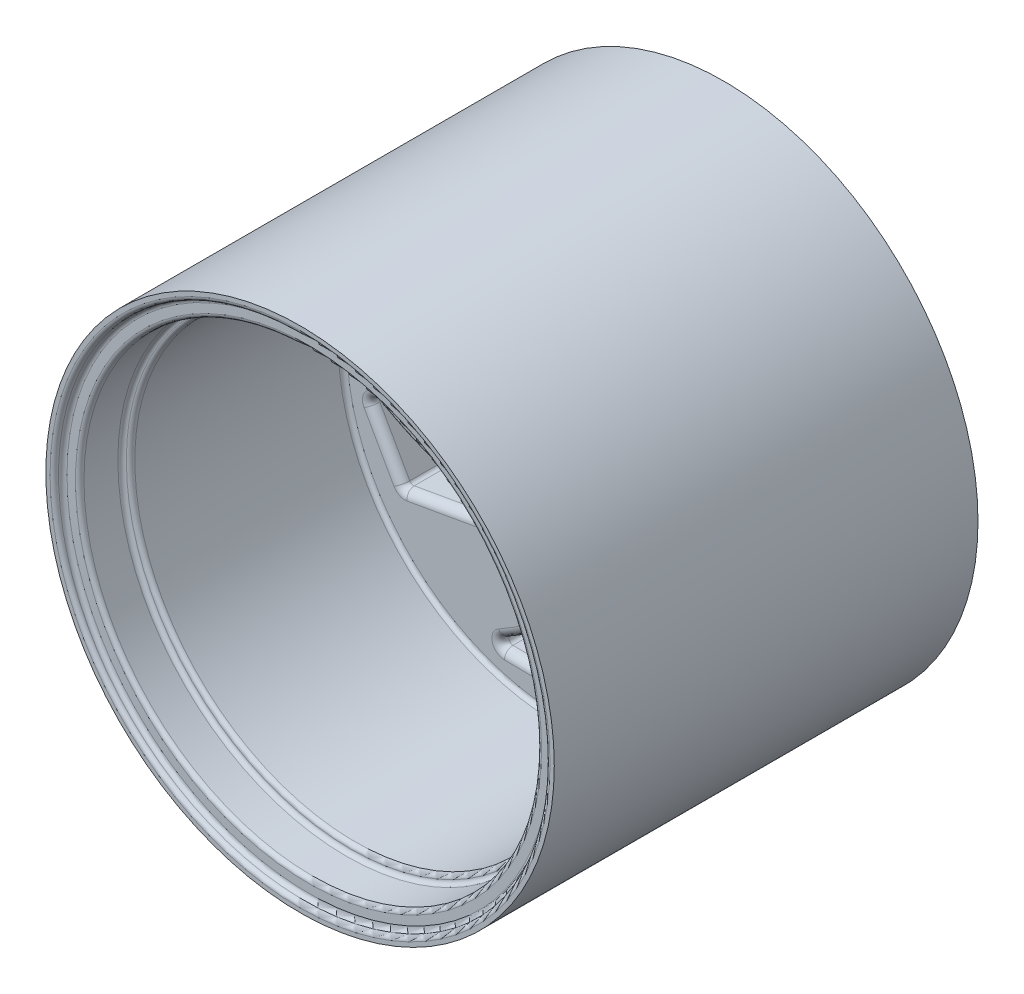
SolidWorks part; units mm, degrees
ref_plane "Ön Düzlem" through (0, 0, 0) normal (0, 0, 1) x (1, 0, 0)
ref_plane "Üst Düzlem" through (0, 0, 0) normal (0, 1, 0) x (1, 0, 0)
ref_plane "Sağ Düzlem" through (0, 0, 0) normal (1, 0, 0) x (0, 0, -1)
sketch "Çizim1" plane through (0, 0, 0) normal (0, 0, 1) x (1, 0, 0)
  circle A0 centre (-8.1488, -1.5541) radius 30
  dimension "D1" = 60
extrude "Yükseklik-Ekstrüzyon1" add sketch "Çizim1" along normal blind 50
sketch "Çizim2" plane through (0, 0, 0) normal (0, 0, -1) x (-1, 0, 0)
  circle A0 centre (8.1488, -1.5541) radius 29
  circle A1 centre (8.1488, -1.5541) radius 30 construction
  dimension "D1" = 1
extrude "Kes-Ekstrüzyon1" cut sketch "Çizim2" against normal blind 1
sketch "Çizim3" plane through (0, 0, 50) normal (0, 0, 1) x (1, 0, 0)
  circle A0 centre (-8.1488, -1.5541) radius 29
  circle A1 centre (-8.1488, -1.5541) radius 30 construction
  dimension "D1" = 1
extrude "Kes-Ekstrüzyon2" cut sketch "Çizim3" against normal blind 1
sketch "Çizim4" plane through (0, 0, 49) normal (0, 0, 1) x (1, 0, 0)
  circle A0 centre (-8.1488, -1.5541) radius 27
  circle A1 centre (-8.1488, -1.5541) radius 29 construction
  dimension "D1" = 2
extrude "Kes-Ekstrüzyon3" cut sketch "Çizim4" against normal blind 5
sketch "Çizim5" plane through (0, 0, 44) normal (0, 0, 1) x (1, 0, 0)
  circle A0 centre (-8.1488, -1.5541) radius 26
  circle A1 centre (-8.1488, -1.5541) radius 27 construction
  dimension "D1" = 1
extrude "Kes-Ekstrüzyon4" cut sketch "Çizim5" against normal blind 25
sketch "Çizim6" plane through (0, 0, 19) normal (0, 0, 1) x (1, 0, 0)
  circle A0 centre (-8.1488, -1.5541) radius 10
  circle A1 centre (-8.1488, -1.5541) radius 8
  circle A2 centre (-8.1488, 4.4459) radius 1
  circle A3 centre (-3.9061, 2.6885) radius 1
  circle A4 centre (-2.1488, -1.5541) radius 1
  circle A5 centre (-3.9061, -5.7967) radius 1
  circle A6 centre (-8.1488, -7.5541) radius 1
  circle A7 centre (-12.3914, -5.7967) radius 1
  circle A8 centre (-14.1488, -1.5541) radius 1
  circle A9 centre (-12.3914, 2.6885) radius 1
  point P23 (-8.1488, -1.5541)
  dimension "D1" = 20
  dimension "D2" = 2
  dimension "D3" = 2
  dimension "D4" = 6
  dimension "D5" = 8
ref_axis "Eksen1" through (-8.1488, -1.5541, 50) along (0, 0, -1)
extrude "Yükseklik-Ekstrüzyon2" add sketch "Çizim6" along normal blind 2 contours A0 A1 | A2 | A8 | A7 | A6 | A5 | A3 | A9 | A4 region at (-17.8659, -1.5541, 19) region at (-8.1488, 4.4459, 19) region at (-3.9061, 2.6885, 19) region at (-3.9061, -5.7967, 19) region at (-8.1488, -7.5541, 19) region at (-12.3914, -5.7967, 19) region at (-14.1488, -1.5541, 19)
sketch "Çizim8" plane through (0, 0, 19) normal (0, 0, 1) x (1, 0, 0)
  circle A0 centre (-8.1488, -1.5541) radius 2
  dimension "D1" = 4
extrude "Kes-Ekstrüzyon5" cut sketch "Çizim8" against normal through all
sketch "Çizim9" plane through (0, 0, 19) normal (0, 0, 1) x (1, 0, 0)
  line L0 (-13.9257, 6.6084) -> (-8.8336, 20.6384)
  line L1 (-8.8336, 20.6384) -> (0.7231, 20.5255)
  line L3 (-3.9683, 7.5301) -> (10.7281, 10.1352)
  line L4 (10.7281, 10.1352) -> (15.4086, 1.8024)
  line L5 (1.8086, -0.6324) -> (11.4129, -12.0573)
  line L6 (11.4129, -12.0573) -> (6.5368, -20.2771)
  line L7 (-2.3718, -9.7166) -> (-7.464, -23.7466)
  line L8 (-7.464, -23.7466) -> (-17.0206, -23.6337)
  line L9 (-12.3293, -10.6383) -> (-27.0257, -13.2434)
  line L10 (-27.0257, -13.2434) -> (-31.7062, -4.9106)
  line L11 (-18.1062, -2.4758) -> (-27.7105, 8.9491)
  line L12 (-30.8072, 6.6742) -> (-25.9311, 14.894) [skipped]
  line L13 (-21.203, -4.7508) -> (-30.8072, 6.6742) [skipped]
  line L14 (-29.7006, -19.3377) -> (-34.3811, -11.0049) [skipped]
  line L15 (-15.0042, -16.7326) -> (-29.7006, -19.3377) [skipped]
  line L16 (-1.5282, -17.3553) -> (-6.6204, -31.3853) [skipped]
  line L17 (-6.6204, -31.3853) -> (-16.177, -31.2724) [skipped]
  line L18 (5.749, -5.9961) -> (15.3533, -17.421) [skipped]
  line L19 (15.3533, -17.421) -> (10.4771, -25.6408) [skipped]
  line L20 (-0.4498, 5.9858) -> (14.2467, 8.5908) [skipped]
  line L21 (14.2467, 8.5908) -> (18.9272, 0.2581) [skipped]
  line L22 (-27.7105, 8.9491) -> (-22.8343, 17.1689)
  circle A0 centre (-8.1488, -1.5541) radius 10 construction
  spline S0 degree 2 poles (0.7231, 20.5255) (-8.7276, 15.9675) (-13.9257, 6.6084) knots 0 0 0 1 1 1
  spline S1 degree 2 poles (15.4086, 1.8024) (6.7359, 7.708) (-3.9683, 7.5301) knots 0 0 0 1 1 1
  spline S2 degree 2 poles (6.5368, -20.2771) (7.3147, -9.8136) (1.8086, -0.6324) knots 0 0 0 1 1 1
  spline S3 degree 2 poles (-17.0206, -23.6337) (-7.5699, -19.0756) (-2.3718, -9.7166) knots 0 0 0 1 1 1
  spline S4 degree 2 poles (-31.7062, -4.9106) (-23.0335, -10.8162) (-12.3293, -10.6383) knots 0 0 0 1 1 1
  spline S5 degree 2 poles (-22.8343, 17.1689) (-23.6123, 6.7054) (-18.1062, -2.4758) knots 0 0 0 1 1 1
  point P29 (-7.727, -5.3734)
  point P55 (-8.1488, -1.5541)
  dimension "D1" = 6
  dimension "D2" = 6
extrude "Kes-Ekstrüzyon6" cut sketch "Çizim9" against normal through all
sketch "Çizim12" plane through (0, 0, 1) normal (0, 0, -1) x (-1, 0, 0)
  circle A0 centre (8.1488, -1.5541) radius 29
extrude "Kes-Ekstrüzyon7" cut sketch "Çizim12" against normal blind 10
sketch "Çizim13" plane through (0, 0, 11) normal (0, 0, -1) x (-1, 0, 0)
  line L0 (25.695, 21.5369) -> (26.0905, 21.2309)
  line L1 (13.3589, -5.1856) -> (13.8988, 1.1423)
  line L2 (13.8988, 1.1423) -> (8.6887, 4.7738)
  line L3 (8.6887, 4.7738) -> (2.9386, 2.0774)
  line L4 (2.9386, 2.0774) -> (2.3988, -4.2505)
  line L5 (2.3988, -4.2505) -> (7.6089, -7.882)
  line L6 (7.6089, -7.882) -> (13.3589, -5.1856)
  line L7 (13.239, 4.6176) -> (26.0905, 21.2309)
  line L8 (12.8435, 4.9235) -> (25.695, 21.5369)
  line L9 (16.1059, -2.3811) -> (36.9193, -5.2041)
  line L10 (16.0387, -2.8765) -> (36.8521, -5.6996)
  line L11 (36.9193, -5.2041) -> (36.8521, -5.6996)
  line L12 (11.4112, -8.8587) -> (19.373, -28.2951)
  line L13 (10.9485, -9.0482) -> (18.9103, -28.4846)
  line L14 (19.373, -28.2951) -> (18.9103, -28.4846)
  line L15 (3.454, -8.0317) -> (-9.3975, -24.6451)
  line L16 (3.0585, -7.7258) -> (-9.7929, -24.3391)
  line L17 (-9.3975, -24.6451) -> (-9.7929, -24.3391)
  line L18 (0.1916, -0.7271) -> (-20.6217, 2.0959)
  line L19 (0.2588, -0.2317) -> (-20.5545, 2.5914)
  line L20 (-20.6217, 2.0959) -> (-20.5545, 2.5914)
  line L21 (4.8864, 5.7505) -> (-3.0755, 25.1869)
  line L22 (5.3491, 5.94) -> (-2.6128, 25.3764)
  line L23 (-3.0755, 25.1869) -> (-2.6128, 25.3764)
  circle A0 centre (8.1488, -1.5541) radius 5.5 construction
  arc A1 (4.8864, 5.7505) -> (0.2588, -0.2317) centre (8.1488, -1.5541) ccw
  arc A2 (12.8435, 4.9235) -> (5.3491, 5.94) centre (8.1488, -1.5541) ccw
  arc A3 (0.1916, -0.7271) -> (3.0585, -7.7258) centre (8.1488, -1.5541) ccw
  arc A4 (3.454, -8.0317) -> (10.9485, -9.0482) centre (8.1488, -1.5541) ccw
  arc A5 (11.4112, -8.8587) -> (16.0387, -2.8765) centre (8.1488, -1.5541) ccw
  arc A6 (16.1059, -2.3811) -> (13.239, 4.6176) centre (8.1488, -1.5541) ccw
  point P37 (8.1488, -1.5541)
  dimension "D2" = 16
  dimension "D1" = 11
  dimension "D3" = 0.5
  dimension "D4" = 6
extrude "Yükseklik-Ekstrüzyon4" add sketch "Çizim13" along normal blind 10
fillet "Radyus1" radius 0.5 6 edges at (17.8512, -1.5541, 19) (20.8512, -1.5541, 50) (20.8512, -1.5541, 49) (18.8512, -1.5541, 49) (18.8512, -1.5541, 44) (17.8512, -1.5541, 44)
fillet "Radyus5" radius 0.5 18 edges at (-22.8343, 17.1689, 15) (-18.1062, -2.4758, 15) (-27.7105, 8.9491, 15) (-12.3293, -10.6383, 15) (-27.0257, -13.2434, 15) (-31.7062, -4.9106, 15) (-17.0206, -23.6337, 15) (-2.3718, -9.7166, 15) (-7.464, -23.7466, 15) (6.5368, -20.2771, 15) (1.8086, -0.6324, 15) (11.4129, -12.0573, 15) (-3.9683, 7.5301, 15) (15.4086, 1.8024, 15) (10.7281, 10.1352, 15) (0.7231, 20.5255, 15) (-13.9257, 6.6084, 15) (-8.8336, 20.6384, 15)
fillet "Radyus6" radius 1 36 edges at (14.3408, 2.944, 19) (12.6652, 6.6867, 19) (10.6798, 10.0329, 19) (5.4279, 9.1957, 19) (0.0646, 7.8091, 19) (-0.7995, 20.1716, 19) (-4.8785, 20.5917, 19) (-8.7692, 20.5454, 19) (-10.67, 15.5786, 19) (-12.1509, 10.2405, 19) (-23.2891, 15.6734, 19) (-25.6925, 12.3509, 19) (-27.5977, 8.9584, 19) (-24.2467, 4.8288, 19) (-20.3643, 0.8773, 19) (-30.6384, -6.0522, 19) (-28.9627, -9.7949, 19) (-26.9773, -13.1411, 19) (-21.7255, -12.3039, 19) (-16.3622, -10.9173, 19) (4.0667, -3.9855, 19) (7.9491, -7.937, 19) (11.3001, -12.0666, 19) (9.3949, -15.4591, 19) (6.9915, -18.7816, 19) (-4.1467, -13.3487, 19) (-5.6275, -18.6867, 19) (-7.5284, -23.6536, 19) (-11.419, -23.6999, 19) (-15.4981, -23.2798, 19)
fillet "Radyus7" radius 0.5 25 edges at (-17.233, 2.6264, 19) (-16.3113, -7.331, 19) (-7.2271, -11.5115, 19) (0.9355, -5.7346, 19) (0.0137, 4.2228, 19) (-9.0705, 8.4033, 19) (-2.9061, -5.7967, 21) (-11.3914, 2.6885, 21) (-11.3914, -5.7967, 19) (-13.1488, -1.5541, 19) (-11.3914, -5.7967, 21) (-7.1488, -7.5541, 19) (-7.1488, -7.5541, 21) (-2.9061, -5.7967, 19) (-1.1488, -1.5541, 19) (-1.1488, -1.5541, 21) (-2.9061, 2.6885, 21) (-7.1488, 4.4459, 19) (-2.9061, 2.6885, 19) (-0.1488, -1.5541, 19) (-7.1488, 4.4459, 21) (-11.3914, 2.6885, 19) (-13.1488, -1.5541, 21) (-0.1488, -1.5541, 21) (1.8512, -1.5541, 21)
